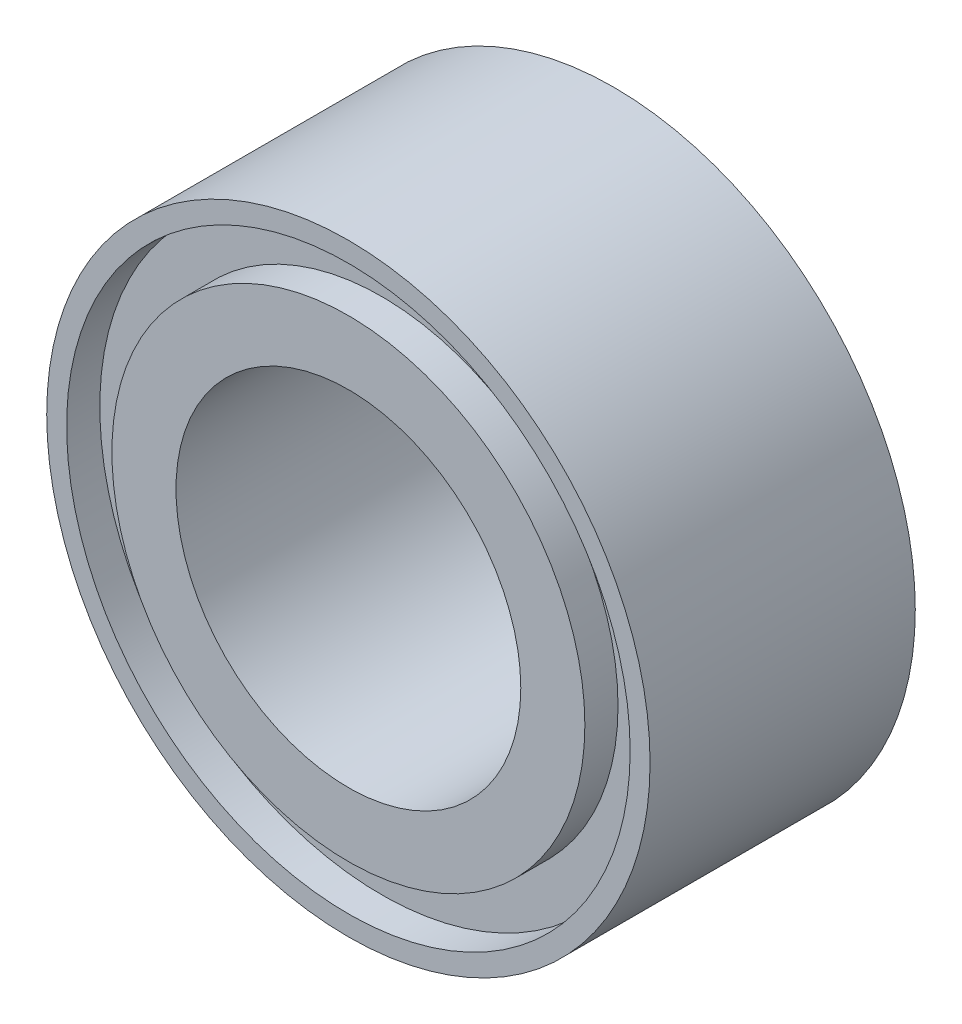
SolidWorks part; units mm, degrees
note: '?' marks a value the reader was unsure of.
ref_plane "Front Plane" through (0, 0, 0) normal (0, 0, 1) x (1, 0, 0)
ref_plane "Top Plane" through (0, 0, 0) normal (0, 1, 0) x (1, 0, 0)
ref_plane "Right Plane" through (0, 0, 0) normal (1, 0, 0) x (0, 0, -1)
sketch "Sketch1" plane through (0, 0, 0) normal (0, 0, 1) x (1, 0, 0)
  circle A0 centre (0, 0) radius 26
  circle A1 centre (0, 0) radius 45.5
  dimension "D1" = 52
  dimension "D2" = 91
extrude "Boss-Extrude1" add sketch "Sketch1" along normal blind 20 contours A1 | A0
sketch "Sketch2" plane through (0, 0, 20) normal (0, 0, 1) x (1, 0, 0)
  line L0 (-395.8118, -201.5493) -> (-56.4701, -206.4053) construction
  circle A0 centre (0, 0) radius 35.6656
  circle A1 centre (0, 0) radius 42.4936
extrude "Cut-Extrude2" cut sketch "Sketch2" against normal blind 5 contours A1
ref_axis "allignment" through (0, 0, -1) along (0, 0, 1)?
mirror "Mirror1" of "Cut-Extrude2", "Boss-Extrude1"
